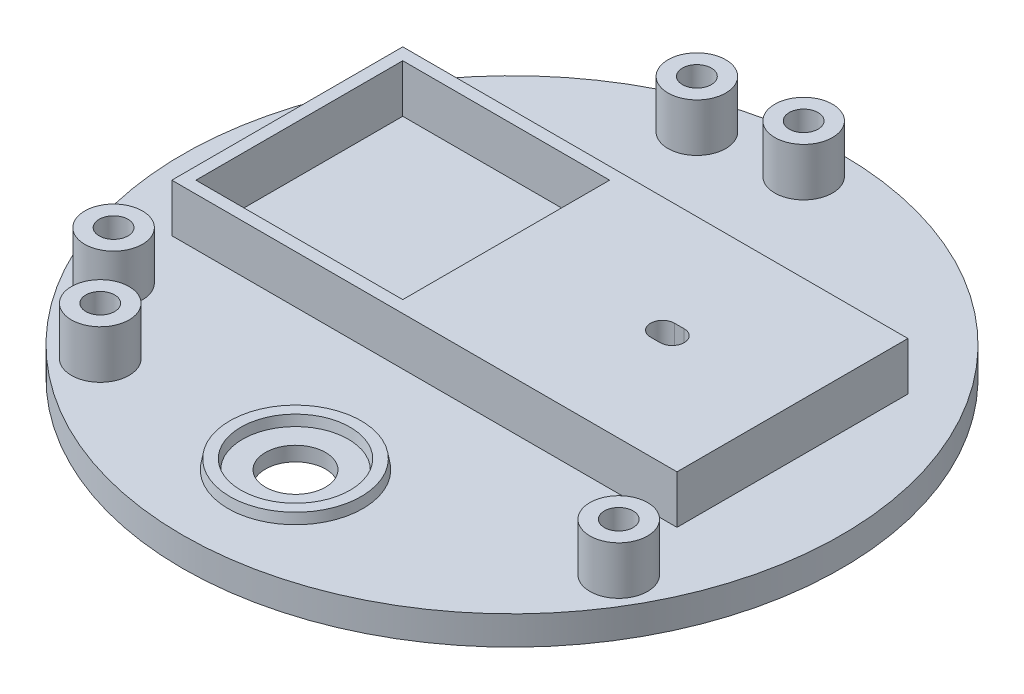
SolidWorks part; units mm, degrees
material "ABS"
ref_plane "Front Plane" through (0, 0, 0) normal (0, 0, 1) x (1, 0, 0)
ref_plane "Top Plane" through (0, 0, 0) normal (0, 1, 0) x (1, 0, 0)
ref_plane "Right Plane" through (0, 0, 0) normal (1, 0, 0) x (0, 0, -1)
sketch "Sketch1" plane through (0, 0, 0) normal (0, 0, 1) x (1, 0, 0)
  line L0 (0, 0) -> (68.5, 0)
  line L1 (68.5, 0) -> (68.5, -6)
  line L2 (68.5, -6) -> (66.5, -6)
  line L3 (66.5, -6) -> (66.5, -3)
  line L5 (53.5, -3) -> (53.5, -6)
  line L6 (53.5, -6) -> (50.5, -6)
  line L7 (50.5, -6) -> (50.5, -3)
  line L8 (50.5, -3) -> (6, -3)
  line L9 (6, -3) -> (6, -5)
  line L10 (6, -5) -> (0, -5)
  line L11 (0, -5) -> (0, 0)
  line L12 (62.3516, -3) -> (66.5, -3)
  line L13 (57.6484, -3) -> (53.5, -3)
  arc A0 (62.3516, -3) -> (57.6484, -3) centre (60, -6.6) ccw
  point P4 (67.5, -6)
  dimension "D2" = 4.3
  dimension "D1" = 60
  dimension "D3" = 6.5
  dimension "D4" = 3
  dimension "D5" = 6.5
  dimension "D6" = 3
  dimension "D7" = 2
  dimension "D8" = 50.5
  dimension "D9" = 0.6
  dimension "D10" = 5
  dimension "D11" = 6
revolve "Revolve1" add sketch "Sketch1" angle 360 about L11
sketch "Sketch2" plane through (0, 0, 0) normal (0, 1, 0) x (1, 0, 0)
  line L0 (-52.5, -30.3109) -> (0, 60.6218) construction
  line L1 (0, 60.6218) -> (52.5, -30.3109) construction
  line L2 (52.5, -30.3109) -> (-52.5, -30.3109) construction
  line L3 (0, 0) -> (0, 60.6218) construction
  line L4 (0, 0) -> (52.5, -30.3109) construction
  line L5 (0, 0) -> (-52.5, -30.3109) construction
  line L6 (0, 0) -> (0, -45) construction
  line L7 (-40.2731, -45.3109) -> (-40.2731, -30.3109) construction
  line L8 (-19.1038, 57.533) -> (-6.1134, 50.033) construction
  circle A0 centre (0, 60.6218) radius 6
  circle A1 centre (0, 60.6218) radius 3
  circle A2 centre (52.5, -30.3109) radius 6
  circle A3 centre (-52.5, -30.3109) radius 6
  circle A4 centre (-52.5, -30.3109) radius 3
  circle A5 centre (52.5, -30.3109) radius 3
  circle A6 centre (0, -45) radius 6.25 construction
  arc A7 (0, 60.6218) -> (-24.7136, -55.3555) centre (0, 0) ccw construction
  circle A8 centre (-40.2731, -45.3109) radius 6
  circle A9 centre (-19.1038, 57.533) radius 6
  circle A10 centre (-40.2731, -45.3109) radius 3
  circle A11 centre (-19.1038, 57.533) radius 3
  arc A12 (15.6635, -19.9954) -> (14.3368, 20.9671) centre (0, 0) ccw construction
  dimension "D2" = 12
  dimension "D3" = 6
  dimension "D5" = 12.5
  dimension "D6" = 12
  dimension "D8" = 6
  dimension "D9" = 25.4
  dimension "D1" = 105
  dimension "D4" = 45
  dimension "D7" = 15
extrude "Boss-Extrude1" add sketch "Sketch2" along normal blind 10
sketch "Sketch3" plane through (0, 0, 0) normal (0, 1, 0) x (1, 0, 0)
  circle A0 centre (0, -45) radius 6.25
  circle A1 centre (0, -45) radius 6.25 construction
extrude "Cut-Extrude1" cut sketch "Sketch3" against normal blind 10
sketch "Sketch4" plane through (0, 0, 0) normal (0, 1, 0) x (1, 0, 0)
  circle A0 centre (0, -45) radius 11
  circle A1 centre (0, -45) radius 14
  dimension "D1" = 22
  dimension "D2" = 28
extrude "Boss-Extrude2" add sketch "Sketch4" along normal blind 2 draft 10
sketch "Sketch5" plane through (0, 0, 0) normal (0, 1, 0) x (1, 0, 0)
  line L0 (50.0131, -15.7216) -> (50.0131, 32.2784)
  line L1 (50.0131, -15.7216) -> (-54.9869, -15.7216)
  line L2 (50.0131, 32.2784) -> (-54.9869, 32.2784)
  line L3 (-54.9869, -15.7216) -> (-54.9869, 32.2784)
  line L5 (-54.9869, 8.2784) -> (50.0131, 8.2784) construction
  line L6 (24.0131, 8.2784) -> (24.0131, 32.2784) construction
  line L7 (25.0131, 8.2784) -> (23.0131, 8.2784) construction
  line L8 (25.0131, 5.7784) -> (23.0131, 5.7784)
  line L9 (25.0131, 10.7784) -> (23.0131, 10.7784)
  line L11 (-52.4869, -13.2216) -> (-52.4869, 29.7784)
  line L12 (-52.4869, 29.7784) -> (-9.4869, 29.7784)
  line L13 (-9.4869, 29.7784) -> (-9.4869, -13.2216)
  line L14 (-9.4869, -13.2216) -> (-52.4869, -13.2216)
  arc A1 (25.0131, 5.7784) -> (25.0131, 10.7784) centre (25.0131, 8.2784) ccw
  arc A2 (23.0131, 10.7784) -> (23.0131, 5.7784) centre (23.0131, 8.2784) ccw
  arc A3 (15.6635, -19.9954) -> (14.3368, 20.9671) centre (0, 0) ccw construction
  point P10 (24.0131, 8.2784)
  point P18 (-9.4869, 8.2784)
  dimension "D3" = 5
  dimension "D1" = 48
  dimension "D2" = 105
  dimension "D4" = 2
  dimension "D5" = 26
  dimension "D6" = 2.5
  dimension "D7" = 43
  dimension "D8" = 43
extrude "Boss-Extrude3" add sketch "Sketch5" along normal blind 10
